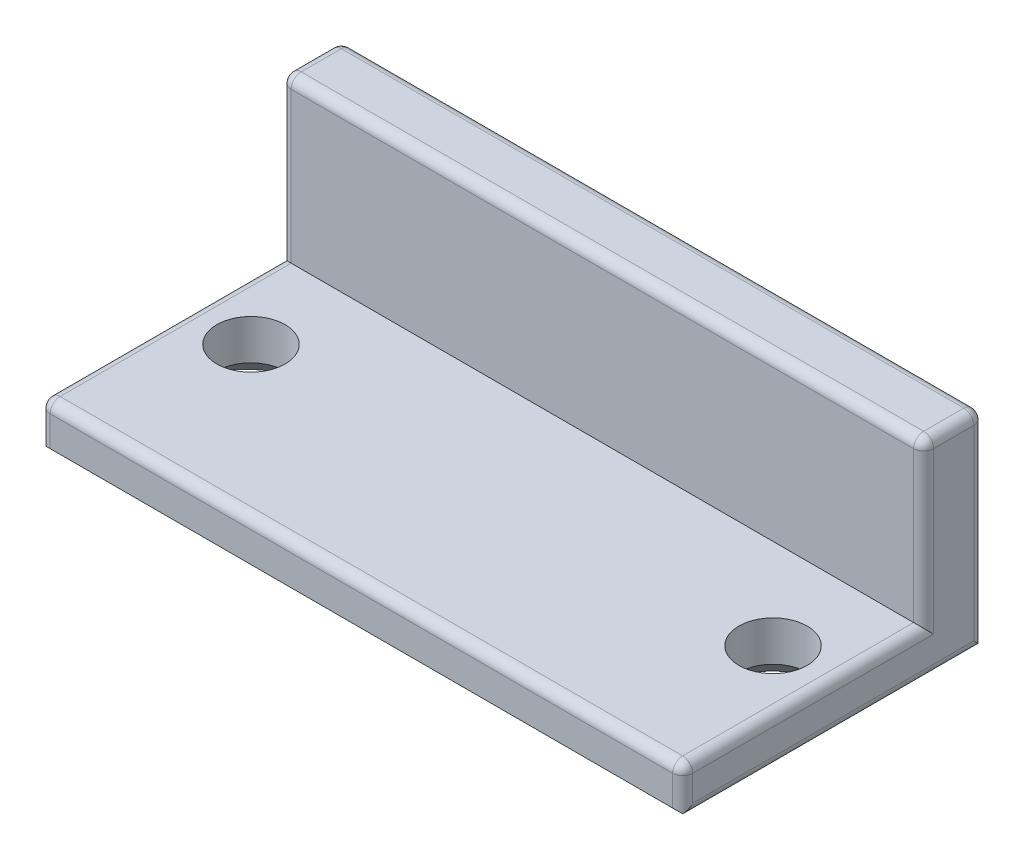
SolidWorks part; units mm, degrees
ref_plane "Спереди" through (0, 0, 0) normal (0, 0, 1) x (1, 0, 0)
ref_plane "Сверху" through (0, 0, 0) normal (0, 1, 0) x (1, 0, 0)
ref_plane "Справа" through (0, 0, 0) normal (1, 0, 0) x (0, 0, -1)
sketch "Эскиз1" plane through (0, 0, 0) normal (0, 1, 0) x (1, 0, 0)
  line L1 (-16, -7.5) -> (16, -7.5)
  line L2 (-16, -7.5) -> (-16, 7.5)
  line L3 (-16, 7.5) -> (16, 7.5)
  line L4 (16, -7.5) -> (16, 7.5)
  line L5 (0, 7.5) -> (0, -7.5) construction
  line L6 (-16, 0) -> (16, 0) construction
  point P0 (0, 0)
  dimension "D1" = 32
  dimension "D2" = 15
extrude "Бобышка-Вытянуть1" add sketch "Эскиз1" along normal blind 3
sketch "Эскиз2" plane through (0, 3, 0) normal (0, 1, 0) x (1, 0, 0)
  line L0 (16, -7.5) -> (16, 7.5) construction
  line L1 (-16, 7.5) -> (16, 7.5)
  line L2 (-16, 7.5) -> (-16, 4.5)
  line L3 (-16, 4.5) -> (16, 4.5)
  line L4 (16, 7.5) -> (16, 4.5)
  dimension "D1" = 3
extrude "Бобышка-Вытянуть2" add sketch "Эскиз2" along normal blind 8
sketch "Эскиз3" plane through (0, 0, 0) normal (0, -1, 0) x (1, 0, 0)
  line L0 (-16, 0) -> (16, 0) construction
  line L1 (-16, -7.5) -> (-16, 7.5) construction
  line L2 (16, 7.5) -> (16, -7.5) construction
  line L3 (0, 9.5274) -> (0, -7.5) construction
  line L4 (16, -7.5) -> (-16, -7.5) construction
  circle A0 centre (13, 0) radius 1.7
  circle A1 centre (-13, 0) radius 1.7
  dimension "D1" = 3.4
  dimension "D2" = 26
extrude "Вырез-Вытянуть1" cut sketch "Эскиз3" against normal blind 8
chamfer "Фаска1" distance 1 angle 45 6 edges at (0, 0, -7.5) (-16, 0, 0) (0, 0, 7.5) (16, 0, 0) (-13, 0, 1.7) (13, 0, -1.7)
fillet "Скругление1" radius 0.5 14 edges at (-16, 7, -4.5) (-16, 3, 1.5) (-16, 2, 7.5) (-16, 1, 0) (-16, 6, -7.5) (0, 11, -7.5) (0, 11, -4.5) (-16, 11, -6) (16, 3, 1.5) (16, 7, -4.5) (16, 11, -6) (16, 6, -7.5) (16, 1, 0) (16, 2, 7.5)
fillet "Скругление2" radius 0.5 3 edges at (-15.8536, 2.8536, 7.3536) (15.8536, 2.8536, 7.3536) (0, 3, 7.5)
